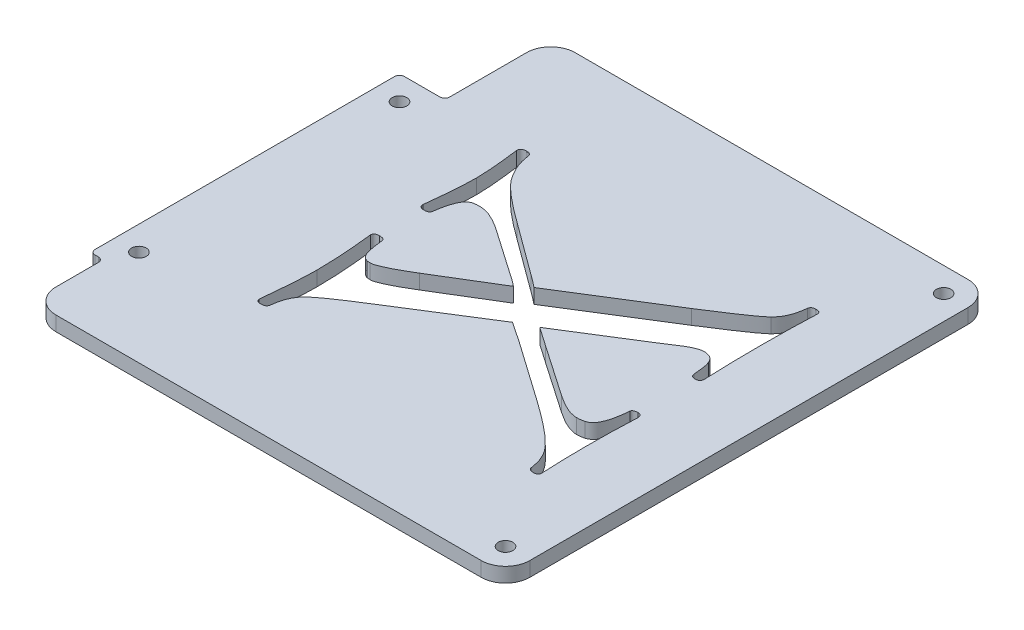
SolidWorks part; units mm, degrees
ref_plane "Front Plane" through (0, 0, 0) normal (0, 0, 1) x (1, 0, 0)
ref_plane "Top Plane" through (0, 0, 0) normal (0, 1, 0) x (1, 0, 0)
ref_plane "Right Plane" through (0, 0, 0) normal (1, 0, 0) x (0, 0, -1)
ref_plane "Plane1" through (0, 23, 0) normal (0, 1, 0) x (1, 0, 0)
sketch "Sketch1" plane through (0, 23, 0) normal (0, 1, 0) x (1, 0, 0)
  line L0 (98.3054, 50) -> (98.3054, 28.2195)
  line L1 (189, 50) -> (98.3054, 50)
  line L2 (189, 50) -> (189, -50)
  line L3 (189, -50) -> (97.6502, -50)
  line L5 (98.3054, 28.2195) -> (89, 28.2195)
  line L6 (89, 28.2195) -> (89, -35.308)
  line L7 (89, -35.308) -> (91.6598, -35.308)
  line L8 (91.6598, -35.308) -> (91.6598, -50)
  line L9 (91.6598, -50) -> (97.6502, -50)
  line L10 (94.8054, 33.2195) -> (98.3054, 33.2195) construction
  line L11 (184, 45) -> (184, 50) construction
  line L12 (93.3054, 31.7195) -> (93.3054, 28.2195) construction
  line L13 (99.4745, -35.308) -> (86.1225, -35.308) construction
  line L14 (88.1598, -40.308) -> (91.6598, -40.308) construction
  line L15 (86.6598, -38.808) -> (86.6598, -35.308) construction
  line L16 (189, 0) -> (190, 0) construction
  line L17 (190, -60) -> (190, 60) construction
  line L18 (105.0183, -40) -> (185.0183, -40) construction
  line L19 (105.0183, -40) -> (105.0183, 40) construction
  line L20 (105.0183, 40) -> (185.0183, 40) construction
  line L21 (185.0183, -40) -> (185.0183, 40) construction
  line L22 (184, 45) -> (189, 45) construction
  line L23 (184, -45) -> (189, -45) construction
  line L24 (184, -45) -> (184, -50) construction
  line L25 (94, 23.2195) -> (94, 28.2195) construction
  line L26 (94, 23.2195) -> (89, 23.2195) construction
  line L27 (94, -30.308) -> (94, -35.308) construction
  line L28 (94, -30.308) -> (89, -30.308) construction
  line L29 (190, -55) -> (190, 55) construction
  circle A0 centre (86.6598, -40.308) radius 1.5 construction
  circle A1 centre (93.3054, 33.2195) radius 1.5 construction
  circle A2 centre (184, 45) radius 1.5 construction
  circle A3 centre (184, 45) radius 1.5 construction
  circle A4 centre (184, -45) radius 1.5 construction
  circle A6 centre (94, 23.2195) radius 1.5 construction
  circle A7 centre (94, -30.308) radius 1.5 construction
  point P32 (185.0183, 0)
  dimension "D1" = 100
  dimension "D2" = 80
  dimension "D3" = 3.5
  dimension "D4" = 5
  dimension "D5" = 1
  dimension "D6" = 100
extrude "Boss-Extrude1" add sketch "Sketch1" along normal blind 3
fillet "Fillet3" radius 5 4 edges at (189, 24.5, -50) (98.3054, 24.5, -50) (91.6598, 24.5, 50) (189, 24.5, 50)
fillet "Fillet2" radius 1 4 edges at (89, 24.5, -28.2195) (98.3054, 24.5, -28.2195) (91.6598, 24.5, 35.308) (89, 24.5, 35.308)
sketch "Sketch2" plane through (0, 23, 0) normal (0, 1, 0) x (1, 0, 0)
  circle A0 centre (184, -45) radius 1.5 construction
  circle A1 centre (184, -45) radius 1.5
  circle A2 centre (94, -30.308) radius 1.5 construction
  circle A3 centre (94, -30.308) radius 1.5
  circle A4 centre (94, 23.2195) radius 1.5 construction
  circle A5 centre (94, 23.2195) radius 1.5
  circle A6 centre (184, 45) radius 1.5 construction
  circle A7 centre (184, 45) radius 1.5
extrude "Cut-Extrude1" cut sketch "Sketch2" along normal up to surface (3 mm away) up to face at (116.9913, 26, 1.7721)
sketch "Sketch4" plane through (0, 23, 0) normal (0, 1, 0) x (1, 0, 0)
  line L0 (177, -28.0588) -> (177, 28.0588) construction
  line L1 (189, -45) -> (189, 45) construction
  text T0 "X" font "@Yu Mincho Demibold" height 60
  dimension "D1" = 12
extrude "Cut-Extrude2" cut sketch "Sketch4" along normal up to surface (3 mm away) up to face at (184, 26, 43.5)
